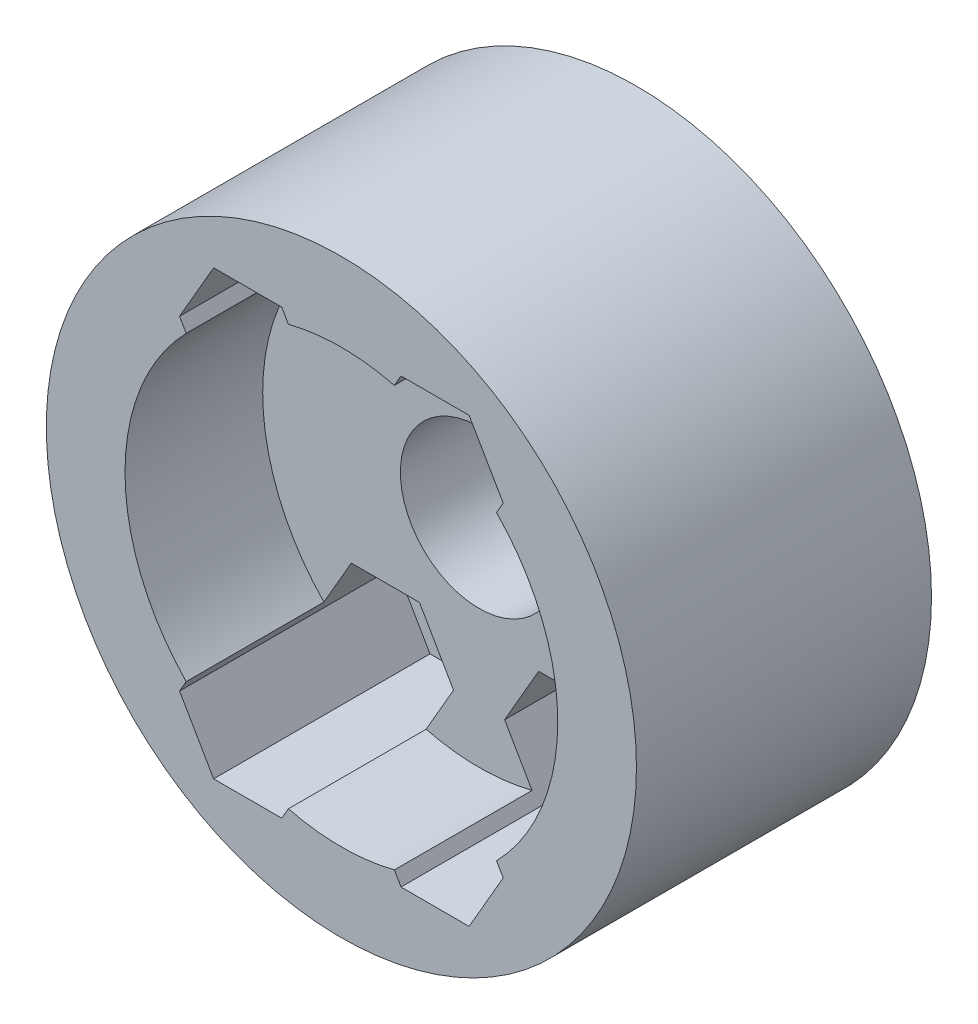
SolidWorks part; units mm, degrees
ref_plane "Front Plane" through (0, 0, 0) normal (0, 0, 1) x (1, 0, 0)
ref_plane "Top Plane" through (0, 0, 0) normal (0, 1, 0) x (1, 0, 0)
ref_plane "Right Plane" through (0, 0, 0) normal (1, 0, 0) x (0, 0, -1)
sketch "Sketch1" plane through (0, 0, 0) normal (0, 0, 1) x (1, 0, 0)
  line L1 (-6.4946, 5.25) -> (-3.0304, 5.25)
  line L2 (-3.0304, 5.25) -> (-1.2984, 8.25)
  line L3 (-1.2984, 8.25) -> (-3.0304, 11.25)
  line L4 (-3.0304, 11.25) -> (-6.4946, 11.25)
  line L5 (-6.4946, 11.25) -> (-8.2266, 8.25)
  line L6 (-8.2266, 8.25) -> (-6.4946, 5.25)
  line L7 (6.4946, 5.25) -> (8.2266, 8.25)
  line L8 (8.2266, 8.25) -> (6.4946, 11.25)
  line L9 (6.4946, 11.25) -> (3.0304, 11.25)
  line L10 (3.0304, 11.25) -> (1.2984, 8.25)
  line L11 (1.2984, 8.25) -> (3.0304, 5.25)
  line L12 (3.0304, 5.25) -> (6.4946, 5.25)
  line L13 (8.2266, -8.25) -> (6.4946, -5.25)
  line L14 (6.4946, -5.25) -> (3.0304, -5.25)
  line L15 (3.0304, -5.25) -> (1.2984, -8.25)
  line L16 (1.2984, -8.25) -> (3.0304, -11.25)
  line L17 (3.0304, -11.25) -> (6.4946, -11.25)
  line L18 (6.4946, -11.25) -> (8.2266, -8.25)
  line L19 (-1.2984, -8.25) -> (-3.0304, -5.25)
  line L20 (-3.0304, -5.25) -> (-6.4946, -5.25)
  line L21 (-6.4946, -5.25) -> (-8.2266, -8.25)
  line L22 (-8.2266, -8.25) -> (-6.4946, -11.25)
  line L23 (-6.4946, -11.25) -> (-3.0304, -11.25)
  line L24 (-3.0304, -11.25) -> (-1.2984, -8.25)
  circle A0 centre (0, 0) radius 4
  circle A1 centre (0, 0) radius 15
  circle A2 centre (-4.7625, -8.25) radius 1.5
  circle A3 centre (4.7625, -8.25) radius 1.5
  circle A4 centre (4.7625, 8.25) radius 1.5
  circle A5 centre (-4.7625, 8.25) radius 1.5
  circle A6 centre (0, 0) radius 11
  circle A7 centre (-4.7625, 8.25) radius 3 construction
  circle A8 centre (4.7625, 8.25) radius 3 construction
  circle A9 centre (4.7625, -8.25) radius 3 construction
  circle A10 centre (-4.7625, -8.25) radius 3 construction
  point P17 (-7.3606, -6.75)
  dimension "D1" = 8
  dimension "D2" = 22
  dimension "D7" = 3
  dimension "D8" = 3
  dimension "D9" = 3
  dimension "D10" = 3
  dimension "D11" = 30
  dimension "D3" = 6
  dimension "D4" = 6
  dimension "D5" = 6
  dimension "D6" = 6
extrude "Boss-Extrude1" add sketch "Sketch1" along normal blind 4 contours L10 A6 L3 L2 L1 L6 L21 L20 L19 L24 L16 L15 L14 L13 L7 L12 L11 A0 | L3 A6 A5 L6 L1 L2 | A6 L3 L4 L5 L6 A5 | A1 A6 L10 L9 L8 L7 L13 L18 L17 L16 L24 L23 L22 L21 L6 L5 L4 L3 | L21 A6 A2 L24 L19 L20 | A6 L21 L22 L23 L24 A2 | A3 A6 | L7 A6 A4 L10 L11 L12 | A6 L7 L8 L9 L10 A4 | L18 L13 L14 L15 L16 L17 region at (-7.118, 6.5004, 0) region at (-4.7625, 4.9389, 0) region at (-5.7928, 10.0348, 0) region at (-5.7928, -10.0348, 0) region at (-7.118, -6.5004, 0) region at (3.9658, 10.1687, 0) region at (5.7928, 10.0348, 0) region at (4.7614, -8.2481, 0) region at (-14.5757, 0, 0)
extrude "Boss-Extrude2" add sketch "Sketch1<3>" along normal blind 11 from surface contours A1 A6 L10 L9 L8 L7 L13 L18 L17 L16 L24 L23 L22 L21 L6 L5 L4 L3 region at (-14.5757, 0, 0) starting at face at (-3.2625, 8.25, 4)
sketch "Sketch1<3>" plane through (0, 0, 0) normal (0, 0, 1) x (1, 0, 0) same geometry as "Sketch1"
extrude "Boss-Extrude3" add sketch "Sketch1<5>" along normal blind 8 contours L10 A6 L3 L2 L1 L6 L21 L20 L19 L24 L16 L15 L14 L13 L7 L12 L11 A0 region at (-4.7625, 4.9389, 0)
sketch "Sketch1<5>" plane through (0, 0, 0) normal (0, 0, 1) x (1, 0, 0) same geometry as "Sketch1"
